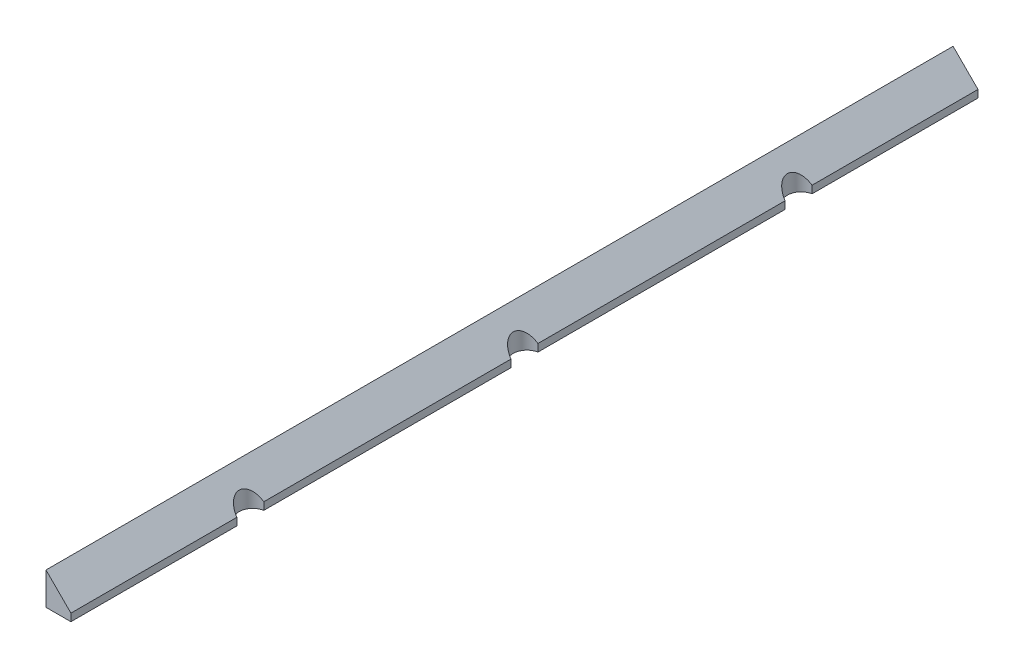
SolidWorks part; units mm, degrees
material "6061-T6 (SS)"
ref_plane "Front Plane" through (0, 0, 0) normal (0, 0, 1) x (1, 0, 0)
ref_plane "Top Plane" through (0, 0, 0) normal (0, 1, 0) x (1, 0, 0)
ref_plane "Right Plane" through (0, 0, 0) normal (1, 0, 0) x (0, 0, -1)
sketch "Sketch1" plane through (0, 0, 0) normal (0, 0, 1) x (1, 0, 0)
  line L5 (0, 0) -> (2.6, 0)
  line L6 (2.6, 0) -> (0, 2.6)
  line L7 (0, 2.6) -> (0, 0)
  line L11 (2, 0) -> (2, 0.6)
  dimension "D1" = 0.6
  dimension "D2" = 2.6
extrude "Boss-Extrude1" add sketch "Sketch1" against normal mid plane 72.8 contours L5 L11 L6 L7 region at (0.7917, 0.9042, 0)
sketch "Sketch2" plane through (0, 0, 0) normal (0, -1, 0) x (1, 0, 0)
  line L0 (2, -36.4) -> (2, 36.4) construction
  circle A12 centre (2.2, 0) radius 1.1
  circle A13 centre (2.2, 22) radius 1.1
  circle A14 centre (2.2, -22) radius 1.1
  dimension "D1" = 2.2
  dimension "D2" = 0.2
  dimension "D3" = 22
  dimension "D4" = 22
extrude "Cut-Extrude1" cut sketch "Sketch2" against normal up to surface (0.4 mm away) up to face at (1, 1.6, 0)
sketch "Sketch3" plane through (0, 0, 0) normal (0, -1, 0) x (1, 0, 0)
  line L1 (2, -20.9183) -> (2, -1.0817) construction
  circle A0 centre (2.2, 0) radius 1
  dimension "D1" = 2
  dimension "D2" = 0.2
extrude "Cut-Extrude2" [suppressed] cut sketch "Sketch3" against normal up to surface (0.4 mm away) up to face at (1.33, 1.27, 0)
sketch "Sketch4" plane through (0, 0, 0) normal (0, -1, 0) x (-1, 0, 0)
  line L0 (0, 36.4) -> (0, -36.4) construction
  line L1 (-2, 36.4) -> (0, 36.4)
  line L2 (-2, 36.4) -> (-2, 24.4)
  line L3 (-2, 24.4) -> (0, 24.4)
  line L4 (0, 36.4) -> (0, 24.4)
  dimension "D1" = 12
extrude "Cut-Extrude3" [suppressed] cut sketch "Sketch4" against normal up to vertex up to point (0, 2.6, -36.4)
